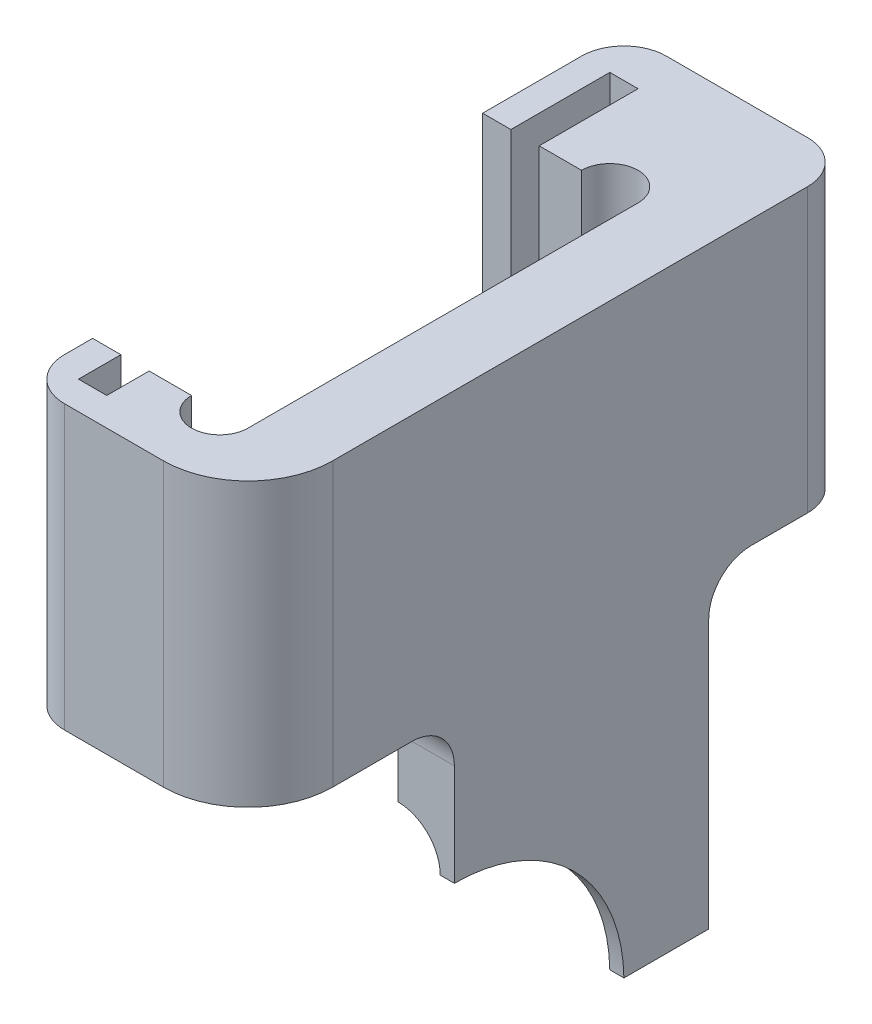
SolidWorks part; units mm, degrees
note: The reader was unsure of these and kept them because the rebuilt part matched: shared geometry of "Sketch9<3>".
ref_plane "Front Plane" through (0, 0, 0) normal (0, 0, 1) x (1, 0, 0)
ref_plane "Top Plane" through (0, 0, 0) normal (0, 1, 0) x (1, 0, 0)
ref_plane "Right Plane" through (0, 0, 0) normal (1, 0, 0) x (0, 0, -1)
sketch "Sketch1" plane through (0, 0, 0) normal (0, 1, 0) x (1, 0, 0)
  line L0 (0, 15.3) -> (0, -12.3)
  line L1 (0, 15.3) -> (-2, 15.3) construction
  line L2 (0, -12.3) -> (-2, -12.3) construction
  line L3 (5, 20.3) -> (5, -17.3)
  line L4 (-4, 15.3) -> (-7, 15.3)
  line L5 (-4, -12.3) -> (-7, -12.3)
  line L6 (-7, 15.3) -> (-7, 20.3)
  line L7 (-7, -12.3) -> (-7, -17.3)
  line L8 (-7, -17.3) -> (5, -17.3)
  line L9 (-7, 20.3) -> (5, 20.3)
  arc A0 (-4, 15.3) -> (0, 15.3) centre (-2, 15.3) cw
  arc A1 (0, -12.3) -> (-4, -12.3) centre (-2, -12.3) cw
  dimension "D5" = 2
  dimension "D6" = 5
  dimension "D1" = 27.6
  dimension "D2" = 15.3
  dimension "D3" = 2
  dimension "D4" = 2
  dimension "D7" = 37.6
  dimension "D8" = 5
  dimension "D9" = 3
  dimension "D10" = 3
  dimension "D11" = 5
  dimension "D12" = 7
  dimension "D13" = 5
  dimension "D14" = 7
extrude "Boss-Extrude1" add sketch "Sketch1" along normal blind 20 contours L0 A1 L5 L7 L8 L3 L9 L6 L4 A0
sketch "Sketch3" plane through (0, 0, -20.3) normal (0, 0, -1) x (-1, 0, 0)
  line L1 (-5, 20) -> (7, 20)
  line L2 (-5, 20) -> (-5, 0)
  line L3 (-5, 0) -> (7, 0)
  line L4 (7, 20) -> (7, 0)
extrude "Boss-Extrude2" add sketch "Sketch3" along normal blind 5
fillet "Fillet1" radius 6 1 edges at (5, 10, 17.3)
fillet "Fillet2" radius 3 1 edges at (5, 10, -25.3)
sketch "Sketch4" plane through (0, 0, -25.3) normal (0, 0, -1) x (-1, 0, 0)
  line L0 (-5, 0) -> (-5, 20) construction
  line L1 (-2, 0) -> (7, 0) construction
  circle A0 centre (0.5, 10) radius 2
  dimension "D1" = 4
  dimension "D2" = 5.5
  dimension "D3" = 10
extrude "Cut-Extrude1" cut sketch "Sketch4" against normal blind 6 contours A0
sketch "Sketch5" plane through (-7, 0, 0) normal (-1, 0, 0) x (0, 0, 1)
  line L0 (12.3, 0) -> (17.3, 0) construction
  line L1 (17.3, 20) -> (15.3, 20)
  line L2 (17.3, 20) -> (17.3, 0)
  line L3 (17.3, 0) -> (15.3, 0)
  line L4 (15.3, 20) -> (15.3, 0)
  line L5 (-15.3, 0) -> (-25.3, 0) construction
  line L6 (-25.3, 20) -> (-22.3, 20)
  line L7 (-25.3, 20) -> (-25.3, 0)
  line L8 (-25.3, 0) -> (-22.3, 0)
  line L9 (-22.3, 20) -> (-22.3, 0)
  dimension "D1" = 2
  dimension "D2" = 3
extrude "Boss-Extrude3" add sketch "Sketch5" along normal blind 4
sketch "Sketch6" plane through (0, 0, 15.3) normal (0, 0, -1) x (-1, 0, 0)
  line L0 (11, 0) -> (7, 0) construction
  line L1 (11, 20) -> (9, 20)
  line L2 (11, 20) -> (11, 0)
  line L3 (11, 0) -> (9, 0)
  line L4 (9, 20) -> (9, 0)
  dimension "D1" = 2
extrude "Boss-Extrude4" add sketch "Sketch6" along normal blind 3
sketch "Sketch7" plane through (0, 0, -22.3) normal (0, 0, 1) x (1, 0, 0)
  line L0 (-11, 0) -> (-1, 0) construction
  line L1 (-11, 20) -> (-9, 20)
  line L2 (-11, 20) -> (-11, 0)
  line L3 (-11, 0) -> (-9, 0)
  line L4 (-9, 20) -> (-9, 0)
  dimension "D1" = 2
extrude "Boss-Extrude5" add sketch "Sketch7" along normal up to surface (7 mm away) up to face at (-5.5, 10, -15.3)
fillet "Fillet3" radius 3 2 edges at (-11, 10, 17.3) (-11, 10, -25.3)
sketch "Sketch8" plane through (0, 0, 0) normal (-1, 0, 0) x (0, 0, 1)
  line L1 (-15.3, 0) -> (2.7, 0)
  line L2 (-15.3, 0) -> (-15.3, -22)
  line L3 (-15.3, -22) -> (2.7, -22)
  line L4 (2.7, 0) -> (2.7, -22)
  dimension "D1" = 18
  dimension "D2" = 22
extrude "Boss-Extrude6" add sketch "Sketch8" against normal blind 5 contours L2 L3 L4 L1
sketch "Sketch9" plane through (0, 0, 0) normal (-1, 0, 0) x (0, 0, 1)
  line L0 (2.7, 0) -> (12.3, 0) construction
  line L1 (-15.3, 0) -> (-15.3, -22) construction
  line L2 (2.7, 0) -> (2.7, -22) construction
  line L3 (-15.3, -22) -> (2.7, -22) construction
  arc A0 (2.7, -7.2) -> (-12.2987, -22) centre (2.7, -22.2) ccw
  arc A1 (2.7, -10.2) -> (-9.2983, -22) centre (2.7, -22.2) ccw
  point P0 (2.7, -22.2)
  line M3 (-15.3, -22) -> (2.7, -22)
  line M4 (2.7, -22) -> (2.7, 0)
  dimension "D3" = 15
  dimension "D4" = 12
  dimension "D1" = 22.2
  dimension "D2" = 18
extrude "Cut-Extrude2" cut sketch "Sketch9" against normal blind 4 and the other way through all contours A0 M4 M3
extrude "Cut-Extrude3" cut sketch "Sketch9<3>" against normal through all and the other way through all contours A1
sketch "Sketch9<3>" plane through (0, 0, 0) normal (-1, 0, 0) x (0, 0, 1) same geometry as "Sketch9"
fillet "Fillet4" radius 3 1 edges at (4, -11.5229, -7.8357)
sketch "Sketch11" plane through (0, 0, 0) normal (-1, 0, 0) x (0, 0, 1)
  line L1 (-15.3, -22) -> (2.7, -22)
  line L2 (-15.3, -22) -> (-15.3, 0)
  line L3 (-15.3, 0) -> (2.7, 0)
  line L4 (2.7, -22) -> (2.7, 0)
extrude "Cut-Extrude4" cut sketch "Sketch11" against normal blind 1
fillet "Fillet5" radius 3 2 edges at (3, 0, -15.3) (3, 0, 2.7)
